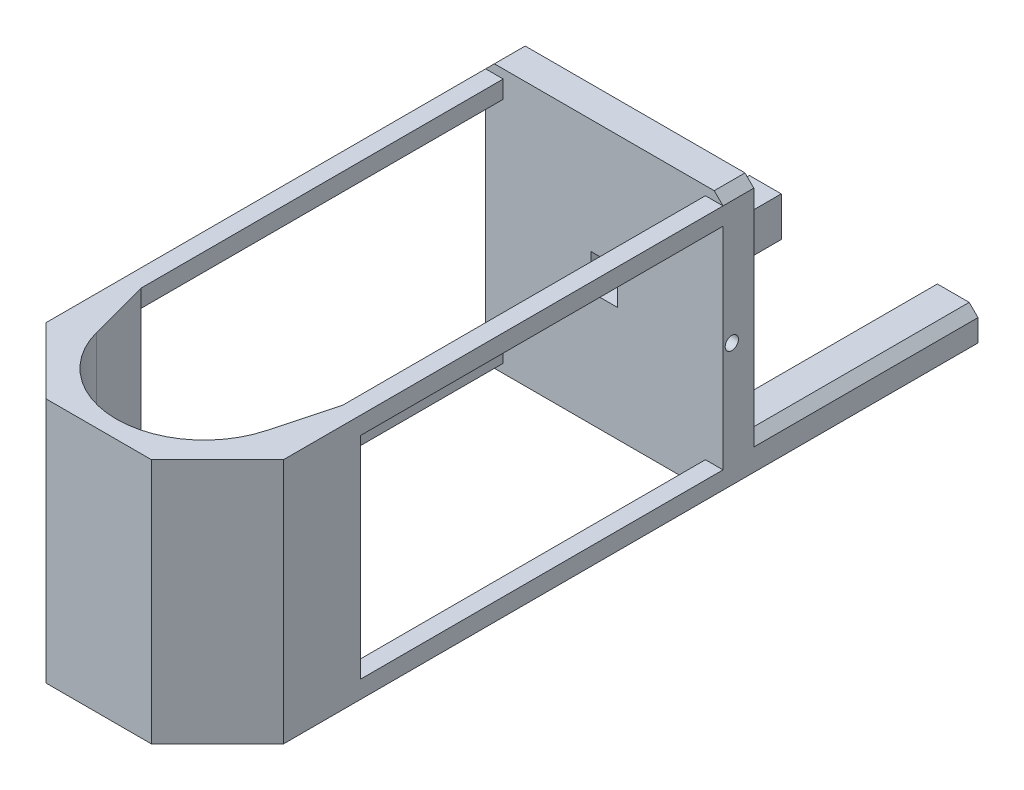
SolidWorks part; units mm, degrees
ref_plane "Front Plane" through (0, 0, 0) normal (0, 0, 1) x (1, 0, 0)
ref_plane "Top Plane" through (0, 0, 0) normal (0, 1, 0) x (1, 0, 0)
ref_plane "Right Plane" through (0, 0, 0) normal (1, 0, 0) x (0, 0, -1)
sketch "Sketch1" plane through (0, 0, 0) normal (0, 0, 1) x (1, 0, 0)
  line L0 (54, 2) -> (54, 7) construction
  line L1 (54, 7) -> (52, 9) construction
  line L2 (52, 9) -> (44.75, 9) construction
  line L3 (44.75, 9) -> (44.75, 0) construction
  line L4 (44.75, 0) -> (52, 0) construction
  line L5 (52, 0) -> (54, 2) construction
  line L6 (0, 7) -> (0, 2) construction
  line L7 (0, 2) -> (2, 0) construction
  line L8 (2, 0) -> (9.25, 0) construction
  line L9 (9.25, 0) -> (9.25, 9) construction
  line L10 (9.25, 9) -> (2, 9) construction
  line L11 (2, 9) -> (0, 7) construction
  line L12 (37.6, 51) -> (52, 51) construction
  line L13 (52, 51) -> (54, 53) construction
  line L14 (54, 53) -> (54, 58) construction
  line L15 (54, 58) -> (52, 60) construction
  line L16 (52, 60) -> (2, 60) construction
  line L17 (2, 60) -> (0, 58) construction
  line L18 (0, 58) -> (0, 53) construction
  line L19 (0, 53) -> (2, 51) construction
  line L20 (2, 51) -> (16.4, 51) construction
  line L21 (16.4, 51) -> (37.6, 51) construction
  line L22 (54, 2) -> (54, 7)
  line L23 (54, 7) -> (52, 9)
  line L24 (52, 9) -> (44.75, 9)
  line L25 (44.75, 9) -> (44.75, 0)
  line L26 (44.75, 0) -> (52, 0)
  line L27 (52, 0) -> (54, 2)
  line L28 (0, 7) -> (0, 2)
  line L29 (0, 2) -> (2, 0)
  line L30 (2, 0) -> (9.25, 0)
  line L31 (9.25, 0) -> (9.25, 9)
  line L32 (9.25, 9) -> (2, 9)
  line L33 (2, 9) -> (0, 7)
  line L34 (37.6, 51) -> (52, 51)
  line L35 (52, 51) -> (54, 53)
  line L36 (54, 53) -> (54, 58)
  line L37 (54, 58) -> (52, 60)
  line L38 (52, 60) -> (2, 60)
  line L39 (2, 60) -> (0, 58)
  line L40 (0, 58) -> (0, 53)
  line L41 (0, 53) -> (2, 51)
  line L42 (2, 51) -> (16.4, 51)
  line L43 (16.4, 51) -> (37.6, 51)
extrude "Boss-Extrude1" add sketch "Sketch1" along normal blind 5 contours L38 L39 L40 L41 L42 L43 L34 L35 L36 L37
sketch "Sketch2" plane through (0, 0, -51) normal (0, 0, 1) x (1, 0, 0)
  line L0 (0, 7) -> (0, 2) construction
  line L1 (0, 2) -> (2, 0) construction
  line L2 (2, 0) -> (9.25, 0) construction
  line L3 (9.25, 0) -> (9.25, 9) construction
  line L4 (9.25, 9) -> (2, 9) construction
  line L5 (2, 9) -> (0, 7) construction
  line L6 (54, 2) -> (54, 7) construction
  line L7 (54, 7) -> (52, 9) construction
  line L8 (52, 9) -> (44.75, 9) construction
  line L9 (44.75, 9) -> (44.75, 0) construction
  line L10 (44.75, 0) -> (52, 0) construction
  line L11 (52, 0) -> (54, 2) construction
  line L12 (0, 7) -> (0, 2)
  line L13 (0, 2) -> (2, 0)
  line L14 (2, 0) -> (9.25, 0)
  line L15 (9.25, 0) -> (9.25, 9)
  line L16 (9.25, 9) -> (2, 9)
  line L17 (2, 9) -> (0, 7)
  line L18 (54, 2) -> (54, 7)
  line L19 (54, 7) -> (52, 9)
  line L20 (52, 9) -> (44.75, 9)
  line L21 (44.75, 9) -> (44.75, 0)
  line L22 (44.75, 0) -> (52, 0)
  line L23 (52, 0) -> (54, 2)
extrude "Boss-Extrude2" add sketch "Sketch2" along normal blind 56 separate body
sketch "Sketch8" plane through (0, 0, 5) normal (0, 0, 1) x (1, 0, 0)
  line L0 (0, 2) -> (0, 58)
  line L1 (2, 60) -> (52, 60)
  line L2 (54, 58) -> (54, 2)
  line L3 (52, 0) -> (2, 0)
  line L4 (52, 60) -> (2, 60) construction
  line L5 (54, 53) -> (54, 58) construction
  line L6 (0, 58) -> (2, 60)
  line L7 (52, 60) -> (54, 58)
  line L8 (54, 2) -> (52, 0)
  line L9 (2, 0) -> (0, 2)
  point P0 (0, 0)
  point P1 (0, 60)
  point P4 (54, 60)
  point P5 (54, 0)
  dimension "D1" = 0
  dimension "D2" = 0
extrude "Boss-Extrude3" add sketch "Sketch8" along normal blind 2 and the other way blind 5
sketch "Sketch9" plane through (0, 0, 7) normal (0, 0, 1) x (1, 0, 0)
  line L1 (24, 34) -> (30, 34)
  line L2 (24, 34) -> (24, 26)
  line L3 (24, 26) -> (30, 26)
  line L4 (30, 34) -> (30, 26)
  line L5 (24, 34) -> (30, 26) construction
  line L6 (24, 26) -> (30, 34) construction
  point P0 (27, 30)
  dimension "D1" = 8
  dimension "D2" = 6
  dimension "D3" = 27
  dimension "D4" = 30
extrude "Cut-Extrude3" cut sketch "Sketch9" against normal blind 6
sketch "Sketch10" plane through (30, 0, 0) normal (-1, 0, 0) x (0, 0, 1)
  line L0 (7, 58) -> (7, 2) construction
  circle A0 centre (5, 30) radius 1.5
  dimension "D1" = 3
  dimension "D2" = 2
  dimension "D3" = 30
extrude "Cut-Extrude4" cut sketch "Sketch10" against normal through all both and the other way through all
sketch "Sketch3" plane through (0, 0, -51) normal (0, 0, 1) x (1, 0, 0)
  circle A0 centre (4.5, 4.5) radius 2.15
  circle A1 centre (4.5, 55.5) radius 2.15
  circle A2 centre (49.5, 55.5) radius 2.15
  circle A3 centre (49.5, 4.5) radius 2.15
  dimension "D1" = 4.3
  dimension "D2" = 4.3
  dimension "D3" = 4.3
  dimension "D4" = 4.3
  dimension "D5" = 51
  dimension "D6" = 0
  dimension "D7" = 45
  dimension "D8" = 51
  dimension "D9" = 45
  dimension "D10" = 0
  dimension "D11" = 4.5
  dimension "D12" = 4.5
sketch "Sketch5" plane through (0, 60, 0) normal (0, 1, 0) x (1, 0, 0)
  line L0 (32.6, 5) -> (21.4, 5)
  line L5 (37.6, 10) -> (37.6, 46)
  line L8 (37.6, 10) -> (32.6, 5)
  line L9 (27, 71.4989) -> (27, -28.5011) construction
  line L11 (16.4, 10) -> (21.4, 5)
  line L12 (16.4, 10) -> (16.4, 46)
  line L14 (16.4, 46) -> (37.6, 46)
sketch3d "3DSketch1" plane through (0, 0, 0) normal (0, 0, 1) x (1, 0, 0)
  dimension "D1" = 30
sketch3d "3DSketch2" plane through (0, 0, 0) normal (0, 0, 1) x (1, 0, 0)
  dimension "D1" = 27
sketch3d "3DSketch3" plane through (0, 0, 0) normal (0, 0, 1) x (1, 0, 0)
  dimension "D1" = 2
sketch "Sketch11" plane through (0, 30, 0) normal (0, 1, 0) x (1, 0, 0)
  line L0 (52, 56) -> (2, 56) construction
  line L2 (27, 71.4989) -> (27, -28.5011) construction
  line L3 (0, -7) -> (54, -7)
  line L4 (54, -7) -> (54, -122)
  line L5 (54, -122) -> (0, -122)
  line L6 (0, -122) -> (0, -7)
  line L8 (52, -7) -> (2, -7) construction
  circle A0 centre (27, -98) radius 20 construction
  dimension "D1" = 40
  dimension "D2" = 154
  dimension "D3" = 0
  dimension "D4" = 24
  dimension "D5" = 54
  dimension "D6" = 0
  dimension "D7" = 0
extrude "Boss-Extrude4" add sketch "Sketch11" along normal blind 28 and the other way blind 28 contours L4 L5 L6 L3
sketch "Sketch12" plane through (0, 58, 0) normal (0, 1, 0) x (1, 0, 0)
  line L0 (0, -122) -> (0, -7) construction
  line L1 (52, 56) -> (2, 56) construction
  line L2 (52, -7) -> (2, -7) construction
  line L4 (4, -89.4369) -> (4, -7)
  line L5 (4, -7) -> (50, -7)
  line L6 (50, -89.4369) -> (50, -7)
  line L7 (54, -7) -> (54, -122) construction
  line L8 (7.6815, -103.1764) -> (4, -89.4369)
  line L9 (46.3185, -103.1764) -> (50, -89.4369)
  line L10 (27, 71.4989) -> (27, -28.5011) construction
  arc A0 (7.6815, -103.1764) -> (46.3185, -103.1764) centre (27, -98) ccw
  dimension "D1" = 40
  dimension "D4" = 0
  dimension "D8" = 0
  dimension "D2" = 27
  dimension "D3" = 154
  dimension "D5" = 4
  dimension "D6" = 4
  dimension "D9" = 15
extrude "Cut-Extrude5" cut sketch "Sketch12" against normal through all
sketch "Sketch13" plane through (27, 0, 0) normal (1, 0, 0) x (0, 0, -1)
  line L0 (-7, 58) -> (-122, 58) construction
  line L1 (-7, 6) -> (-89.4369, 6)
  line L2 (-7, 6) -> (-7, 54)
  line L3 (-7, 54) -> (-89.4369, 54)
  line L4 (-89.4369, 6) -> (-89.4369, 54)
  line L6 (-89.4369, 2) -> (-89.4369, 58) construction
  line L7 (-7, 2) -> (-122, 2) construction
  line L8 (-7, 58) -> (-7, 60) construction
  dimension "D1" = 4
  dimension "D2" = 0
  dimension "D3" = 4
  dimension "D4" = 0
extrude "Cut-Extrude6" cut sketch "Sketch13" against normal through all both and the other way through all
chamfer "Chamfer1" distance 15 angle 45 1 edges at (0, 30, 122)
chamfer "Chamfer2" distance 15 angle 45 1 edges at (54, 30, 122)
